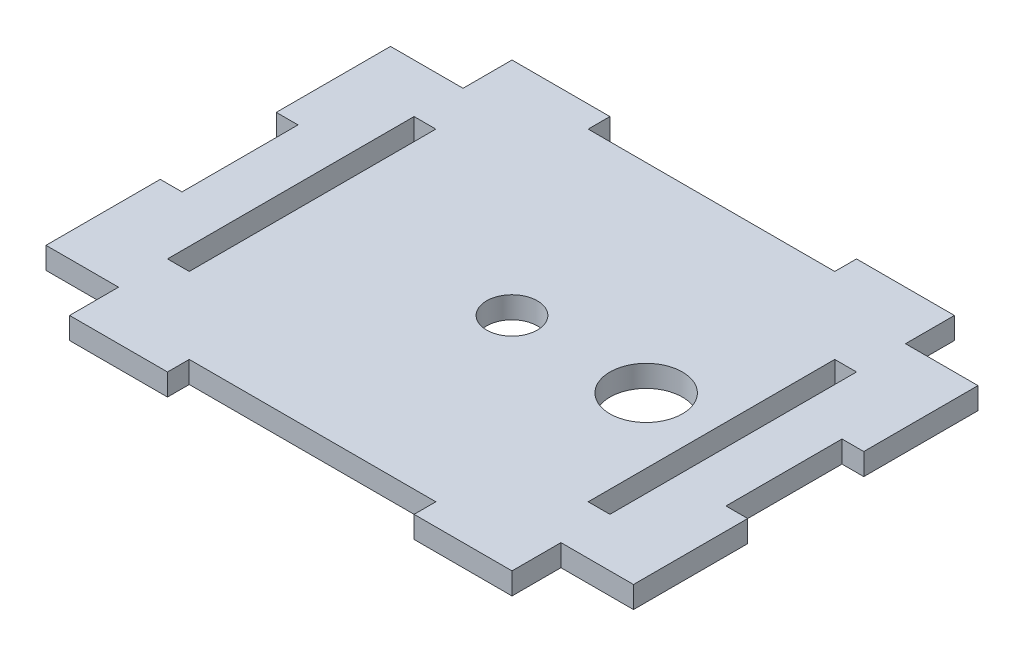
SolidWorks part; units mm, degrees
ref_plane "Alzado" through (0, 0, 0) normal (0, 0, 1) x (1, 0, 0)
ref_plane "Planta" through (0, 0, 0) normal (0, 1, 0) x (1, 0, 0)
ref_plane "Vista lateral" through (0, 0, 0) normal (1, 0, 0) x (0, 0, -1)
sketch "Croquis1" plane through (0, 0, 0) normal (0, 1, 0) x (1, 0, 0)
  line L0 (-27.5, 0) -> (-27.5, 17)
  line L1 (-27.5, 0) -> (-27.5, -17)
  line L2 (-27.5, -17) -> (-30.5, -17)
  line L3 (-30.5, -17) -> (-30.5, 17)
  line L4 (-30.5, 17) -> (-27.5, 17)
  line L5 (0, 27.5) -> (17, 27.5)
  line L6 (17, 30.5) -> (17, 27.5)
  line L7 (-30.5, 23.75) -> (-30.5, 30.5)
  line L8 (0, 27.5) -> (-17, 27.5)
  line L9 (-17, 27.5) -> (-17, 30.5)
  line L10 (27.5, 0) -> (27.5, -17)
  line L11 (30.5, -17) -> (27.5, -17)
  line L12 (30.5, 17) -> (30.5, -17)
  line L13 (27.5, 0) -> (27.5, 17)
  line L14 (27.5, 17) -> (30.5, 17)
  line L15 (0, -27.5) -> (-17, -27.5)
  line L16 (-17, -30.5) -> (-17, -27.5)
  line L17 (-30.5, 30.5) -> (-23.75, 30.5)
  line L18 (0, -27.5) -> (17, -27.5)
  line L19 (17, -27.5) -> (17, -30.5)
  line L20 (23.75, 30.5) -> (30.5, 30.5)
  line L21 (30.5, 30.5) -> (30.5, 23.75)
  line L22 (-37.5, 0) -> (-37.5, 8)
  line L23 (-37.5, 8) -> (-40.5, 8)
  line L24 (23.75, -30.5) -> (30.5, -30.5)
  line L25 (-40.5, -8) -> (-37.5, -8)
  line L26 (-37.5, -8) -> (-37.5, 0)
  line L27 (23.75, 30.5) -> (17, 30.5)
  line L28 (30.5, -30.5) -> (30.5, -17)
  line L29 (-30.5, 23.75) -> (-40.5, 23.75)
  line L30 (-40.5, 8) -> (-40.5, 23.75)
  line L31 (-23.75, -30.5) -> (-30.5, -30.5)
  line L32 (-23.75, 30.5) -> (-17, 30.5)
  line L33 (0, 0) -> (18.5, 0) construction
  line L34 (40.5, 8) -> (40.5, 23.75)
  line L35 (30.5, 23.75) -> (40.5, 23.75)
  line L36 (37.5, -8) -> (37.5, 0)
  line L37 (40.5, -8) -> (37.5, -8)
  line L38 (-30.5, -30.5) -> (-30.5, -23.75)
  line L39 (37.5, 8) -> (40.5, 8)
  line L40 (37.5, 0) -> (37.5, 8)
  line L41 (-40.5, -8) -> (-40.5, -23.75)
  line L42 (-30.5, -23.75) -> (-40.5, -23.75)
  line L44 (-23.75, -30.5) -> (-17, -30.5)
  line L45 (23.75, -30.5) -> (17, -30.5)
  line L47 (30.5, -23.75) -> (40.5, -23.75)
  line L48 (40.5, -8) -> (40.5, -23.75)
  line L49 (17, -30.5) -> (-17, -30.5) [skipped]
  line L50 (-17, 30.5) -> (17, 30.5) [skipped]
  circle A0 centre (0, 0) radius 27.5 construction
  circle A1 centre (0, 0) radius 3.5
  circle A2 centre (0, 0) radius 23.5 construction
  circle A3 centre (18.5, 0) radius 5
  point P27 (0, 0)
  dimension "D1" = 55
  dimension "D2" = 7
  dimension "D7" = 47
  dimension "D12" = 10
  dimension "D3" = 17
  dimension "D4" = 17
  dimension "D5" = 3
  dimension "D8" = 37.5
  dimension "D9" = 8
  dimension "D10" = 3
  dimension "D11" = 16
  dimension "D13" = 18.5
  dimension "D6" = 4
extrude "Saliente-Extruir1" add sketch "Croquis1" along normal blind 3 contours L48 L37 L36 L40 L39 L34 L35 L21 L20 L27 L6 L5 L8 L9 L32 L17 L7 L29 L30 L23 L22 L26 L25 L41 L42 L38 L31 L44 L16 L15 L18 L19 L45 L24 L28 L11 L10 L13 L14 L12 L47 A3 A1 L3 L4 L0 region at (8.5, 0, -26.486)
